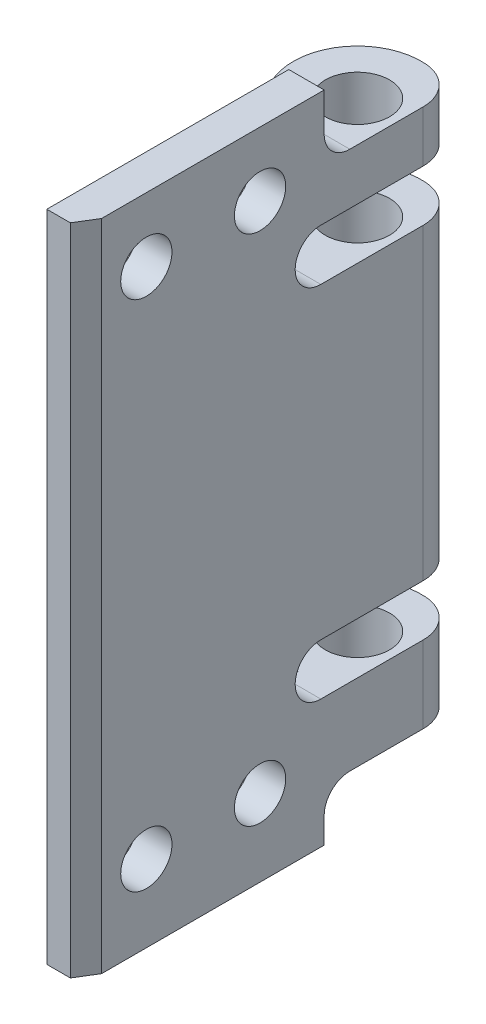
SolidWorks part; units mm, degrees
ref_plane "Front Plane" through (0, 0, 0) normal (0, 0, 1) x (1, 0, 0)
ref_plane "Top Plane" through (0, 0, 0) normal (0, 1, 0) x (1, 0, 0)
ref_plane "Right Plane" through (0, 0, 0) normal (1, 0, 0) x (0, 0, -1)
sketch "Sketch1" plane through (0, 0, 0) normal (0, 1, 0) x (1, 0, 0)
  line L0 (143.3333, 493) -> (716.6667, 493) construction
  line L1 (57.1966, 9.0284) -> (57.1966, 28.64)
  line L4 (59.9567, 29.7327) -> (59.9567, 10.5387)
  line L5 (59.9567, 10.5387) -> (59.0306, 9.0284)
  line L6 (59.0306, 9.0284) -> (57.1966, 9.0284)
  line L7 (59.9567, 29.7327) -> (59.9567, 37.5187)
  line L8 (64.209, 27.9079) -> (65.0991, 27.0179)
  line L13 (64.654, 7.1943) -> (64.654, 5.5805)
  line L16 (63.4817, 13.8234) -> (63.1068, 13.4485)
  arc A1 (59.9567, 37.5187) -> (57.1966, 28.64) centre (56.819, 33.6257) ccw
  circle A4 centre (56.819, 33.6257) radius 2.5
extrude "Boss-Extrude1" add sketch "Sketch1" along normal blind 51 contours L13 L8 L4 L16 | L1 L6 L5 L4 A4 region at (57.3647, 0, -25.9901)
sketch "Sketch2" plane through (59.9567, 0, 0) normal (1, 0, 0) x (0, 0, -1)
  line L0 (0, 0) -> (0, 10) construction
  line L2 (39.1338, 10) -> (25.6338, 10)
  line L11 (39.1338, 14) -> (39.1338, 10)
  line L14 (39.1338, 14) -> (27.8951, 14)
  line L15 (25.6338, 10) -> (25.6338, 14)
  line L18 (25.6338, 14) -> (27.8951, 14)
extrude "Cut-Extrude1" cut sketch "Sketch2" against normal mid plane 30
sketch "Sketch3" plane through (59.9567, 0, 0) normal (1, 0, 0) x (0, 0, -1)
  line L0 (9.0284, 51) -> (9.0284, 40) construction
  line L1 (9.0284, 51) -> (9.0284, 0) construction
  line L3 (25.6338, 14) -> (25.6338, 47.1784) construction
  line L12 (41.7113, 42) -> (27.8951, 42)
  line L14 (41.7113, 42) -> (41.7113, 38)
  line L18 (41.7113, 38) -> (25.6338, 38)
  line L20 (25.6338, 38) -> (25.6338, 42)
  line L21 (25.6338, 42) -> (27.8951, 42)
extrude "Cut-Extrude2" cut sketch "Sketch3" against normal mid plane 25
sketch "Sketch4" plane through (59.9567, 0, 0) normal (1, 0, 0) x (0, 0, -1)
  line L1 (38.8451, 0) -> (38.8451, 4)
  line L4 (38.8451, 51) -> (30.0565, 51)
  line L6 (38.8451, 4) -> (27.8951, 4)
  line L13 (27.8951, 4) -> (27.8951, 0)
  line L17 (38.8451, 0) -> (27.8951, 0)
  line L20 (27.8951, 47) -> (27.8951, 51)
  line L21 (27.8951, 51) -> (30.0565, 51)
  line L23 (38.8451, 51) -> (38.8451, 46)
  line L24 (38.8451, 46) -> (27.8951, 46)
  line L25 (27.8951, 46) -> (27.8951, 47)
extrude "Cut-Extrude3" cut sketch "Sketch4" against normal mid plane 50
sketch "Sketch5" plane through (57.1966, 0, 0) normal (-1, 0, 0) x (0, 0, 1)
  line L0 (-27.8951, 51) -> (-22.8951, 51) construction
  line L1 (-9.0284, 51) -> (-27.8951, 51) construction
  line L2 (-22.8951, 51) -> (-22.8951, 46) construction
  line L3 (-18.4617, 51) -> (-18.4617, 40.0063) construction
  line L4 (-27.8951, 26) -> (-14.7419, 26) construction
  circle A0 centre (-22.8951, 46) radius 2
  circle A1 centre (-14.0284, 46) radius 2
  circle A2 centre (-14.0284, 6) radius 2
  circle A3 centre (-22.8951, 6) radius 2
extrude "Cut-Extrude4" cut sketch "Sketch5" against normal blind 10
fillet "Fillet4" radius 2 1 edges at (57.1966, 26, -28.64)
fillet "Fillet5" radius 3 3 edges at (59.9567, 7, -37.5187) (59.9567, 26, -37.5187) (59.9567, 44, -37.5187)
fillet "Fillet6" radius 2 6 edges at (58.5767, 4, -27.8951) (58.5767, 46, -27.8951) (58.5767, 10, -25.6338) (58.5767, 14, -25.6338) (58.5767, 42, -25.6338) (58.5767, 38, -25.6338)
ref_plane "Plane1" through (0, 30, 0) normal (0, 1, 0) x (1, 0, 0)
sketch "Sketch6" plane through (0, 30, 0) normal (0, 1, 0) x (1, 0, 0)
  line L0 (57.1966, 9.0284) -> (57.1966, 27.8951) construction
  line L1 (57.1966, 23.2078) -> (57.1966, 15.8804)
  circle A0 centre (55.5117, 19.7521) radius 1.5
  arc A1 (55.5117, 21.7521) -> (55.5117, 17.7521) centre (55.5117, 19.7521) ccw
  spline S0 degree 2 poles (55.5117, 21.7521) (56.7322, 22.0656) (57.1966, 23.2078) knots 0 0 0 1 1 1
  spline S1 degree 2 poles (55.5117, 17.7521) (56.9099, 17.3168) (57.1966, 15.8804) knots 0 0 0 1 1 1
  dimension "D1" = 3
  dimension "D2" = 4
extrude "Boss-Extrude2" add sketch "Sketch6" along normal blind 5
